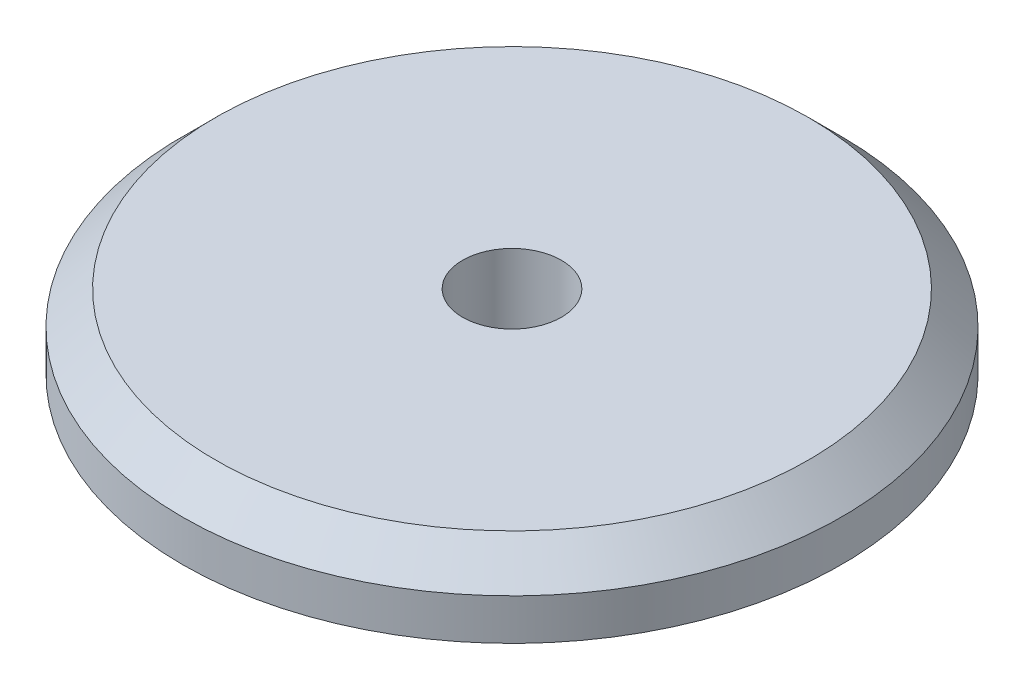
SolidWorks part; units mm, degrees
ref_plane "Front Plane" through (0, 0, 0) normal (0, 0, 1) x (1, 0, 0)
ref_plane "Top Plane" through (0, 0, 0) normal (0, 1, 0) x (1, 0, 0)
ref_plane "Right Plane" through (0, 0, 0) normal (1, 0, 0) x (0, 0, -1)
sketch "Sketch3" plane through (0, 0, 0) normal (0, 1, 0) x (1, 0, 0)
  circle A0 centre (0, 0) radius 100
  dimension "D1" = 200
extrude "Boss-Extrude1" add sketch "Sketch3" along normal blind 22.5
chamfer "Chamfer1" distance 10 angle 45 1 edges at (0, 22.5, 100)
sketch "Sketch4" plane through (0, 0, 0) normal (0, 0, 1) x (1, 0, 0)
  line L0 (-75.6309, 0) -> (-72.4805, 9.696)
  line L1 (-100, 0) -> (100, 0) construction
  line L2 (-72.4805, 9.696) -> (-71.9098, 9.5106)
  line L3 (-71.9098, 9.5106) -> (-75, 0)
  line L4 (-75.6309, 0) -> (-75, 0)
  line L5 (0, 27.0337) -> (0, -14.7835) construction
  dimension "D1" = 10
  dimension "D2" = 0.6
  dimension "D3" = 108
  dimension "D4" = 75
extrude "Cut-Extrude1" cut sketch "Sketch4" against normal blind 25.25 and the other way blind 25.25
pattern_circular "CirPattern1" count 6 over 360 about axis through (0, 27.0337, 0) along (0, -1, 0) of "Cut-Extrude1"
sketch "Sketch5" plane through (0, 22.5, 0) normal (0, 1, 0) x (1, 0, 0)
  circle A0 centre (0, 0) radius 15
  dimension "D1" = 30
extrude "Cut-Extrude2" cut sketch "Sketch5" against normal up to surface (22.5 mm away) up to face at (37.6577, 0, 65.2251)
equation "\"length\"= 50mm'Length of flexture"
equation "\"T\"= 0.6mm'Thickness of Flexture +/- 0.1 mm tolerance"
